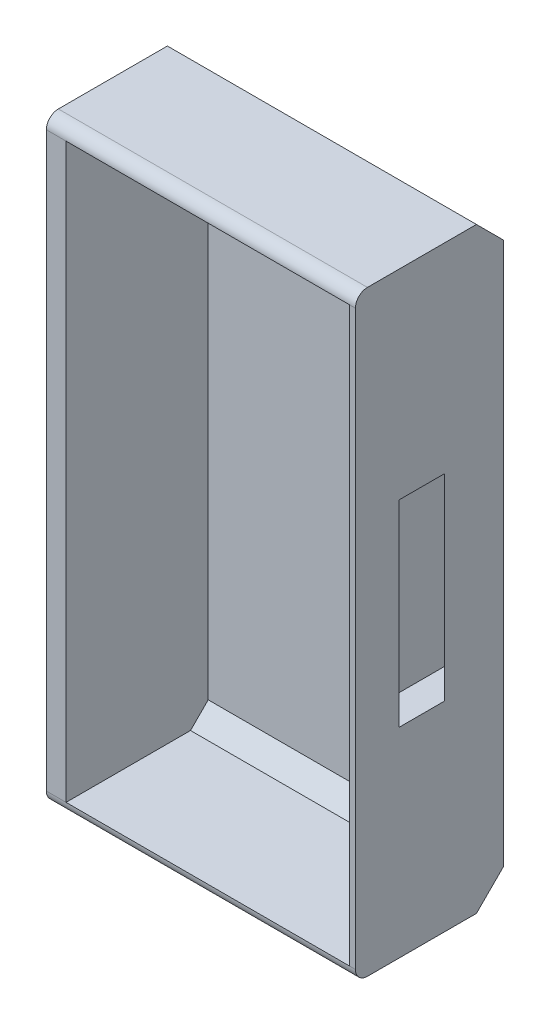
SolidWorks part; units mm, degrees
ref_plane "Front Plane" through (0, 0, 0) normal (1, 0, 0) x (0, 1, 0)
ref_plane "Top Plane" through (0, 0, 0) normal (0, 0, 1) x (0, 1, 0)
ref_plane "Right Plane" through (0, 0, 0) normal (0, 1, 0) x (-1, 0, 0)
sketch "Sketch1" plane through (0, 0, 0) normal (1, 0, 0) x (0, 1, 0)
  line L12 (-98.46, -42.4834) -> (-89.4834, -51.46)
  line L13 (-89.4834, -51.46) -> (89.4834, -51.46)
  line L14 (89.4834, -51.46) -> (98.46, -42.4834)
  line L15 (98.46, -42.4834) -> (98.46, -6.5)
  line L16 (94.5, -2.54) -> (-94.5, -2.54)
  line L17 (-98.46, -6.5) -> (-98.46, -42.4834)
  line L18 (-98.46, -42.4834) -> (-89.4834, -51.46)
  line L19 (-89.4834, -51.46) -> (89.4834, -51.46)
  line L20 (89.4834, -51.46) -> (98.46, -42.4834)
  line L21 (98.46, -42.4834) -> (98.46, -6.5)
  line L22 (94.5, -2.54) -> (-94.5, -2.54)
  line L23 (-98.46, -6.5) -> (-98.46, -42.4834)
  arc A4 (98.46, -6.5) -> (94.5, -2.54) centre (94.5, -6.5) ccw
  arc A5 (-94.5, -2.54) -> (-98.46, -6.5) centre (-94.5, -6.5) ccw
  arc A6 (98.46, -6.5) -> (94.5, -2.54) centre (94.5, -6.5) ccw
  arc A7 (-94.5, -2.54) -> (-98.46, -6.5) centre (-94.5, -6.5) ccw
  dimension "D1" = 0.04
extrude "Boss-Extrude1" add sketch "Sketch1" along normal up to surface (102 mm away) contours L18 L19 L20 L21 A6 L22 A7 L23
ref_plane "Plane3" through (0, 0, 0) normal (0, 1, 0) x (1, 0, 0)
sketch "Sketch11" plane through (0, 0, 0) normal (0, 1, 0) x (1, 0, 0)
  line L0 (102, 24.4917) -> (104.8284, 21.6633)
  line L1 (102, 6.5) -> (102, 42.4834) construction
  line L2 (102, 24.4917) -> (92.1005, 34.3912)
  dimension "D1" = 14
  dimension "D2" = 4
  dimension "D3" = 45
sketch "Sketch12" plane through (102, 0, 0) normal (1, 0, 0) x (0, 1, 0)
  line L0 (0, -24.4917) -> (0, -21.6633) construction
  line L1 (-32.5, -31.9917) -> (32.5, -31.9917)
  line L2 (-32.5, -31.9917) -> (-32.5, -16.9917)
  line L3 (-32.5, -16.9917) -> (32.5, -16.9917)
  line L4 (32.5, -31.9917) -> (32.5, -16.9917)
  line L5 (-32.5, -31.9917) -> (32.5, -16.9917) construction
  line L6 (-32.5, -16.9917) -> (32.5, -31.9917) construction
  line L7 (0, -24.4917) -> (0, -34.3912) construction
  line L10 (89.4834, -51.46) -> (-89.4834, -51.46) construction
  point P0 (0, -24.4917)
  dimension "D1" = 65
  dimension "D2" = 15
  dimension "D3" = 26.9683
sweep "Cut-Sweep1" cut profiles "Sketch12" path "Sketch11"
shell "Shell1" thickness 2 removed face at (51, 0, -2.54)
sketch "Sketch8" plane through (2, 0, 0) normal (1, 0, 0) x (0, 1, 0)
  line L11 (-10, -27) -> (-10, -17)
  line L12 (-10, -17) -> (10, -17)
  line L13 (10, -27) -> (10, -17)
  line L15 (-98.46, -42.4834) -> (-89.4834, -51.46)
  line L16 (-89.4834, -51.46) -> (89.4834, -51.46)
  line L17 (89.4834, -51.46) -> (98.46, -42.4834)
  line L18 (98.46, -42.4834) -> (98.46, -6.5)
  line L19 (94.5, -2.54) -> (-94.5, -2.54)
  line L20 (-98.46, -6.5) -> (-98.46, -42.4834)
  line L21 (-98.46, -42.4834) -> (-89.4834, -51.46)
  line L22 (-89.4834, -51.46) -> (89.4834, -51.46)
  line L23 (89.4834, -51.46) -> (98.46, -42.4834)
  line L24 (98.46, -42.4834) -> (98.46, -6.5)
  line L25 (94.5, -2.54) -> (-94.5, -2.54)
  line L26 (-98.46, -6.5) -> (-98.46, -42.4834)
  arc A0 (-10, -27) -> (10, -27) centre (0, -27) ccw
  arc A5 (98.46, -6.5) -> (94.5, -2.54) centre (94.5, -6.5) ccw
  arc A6 (-94.5, -2.54) -> (-98.46, -6.5) centre (-94.5, -6.5) ccw
  arc A7 (98.46, -6.5) -> (94.5, -2.54) centre (94.5, -6.5) ccw
  arc A8 (-94.5, -2.54) -> (-98.46, -6.5) centre (-94.5, -6.5) ccw
  point P4 (0, -51.46)
  dimension "D2" = 20
  dimension "D3" = 24.46
  dimension "D4" = 10
  dimension "D5" = 20
  dimension "D1" = 0
extrude "Boss-Extrude2" add sketch "Sketch8" along normal blind 2.5
sketch "Sketch10" plane through (4.5, 0, 0) normal (1, 0, 0) x (0, 1, 0)
  line L8 (94.5, -4.54) -> (94.5, -2.54)
  line L9 (94.5, -2.54) -> (-94.5, -2.54)
  line L10 (-94.5, -2.54) -> (-94.5, -4.54)
  line L11 (-96.46, -6.5) -> (-96.46, -41.655)
  line L12 (-96.46, -41.655) -> (-88.655, -49.46)
  line L13 (-88.655, -49.46) -> (88.655, -49.46)
  line L14 (88.655, -49.46) -> (96.46, -41.655)
  line L15 (96.46, -41.655) -> (96.46, -6.5)
  line L16 (94.5, -4.54) -> (94.5, -2.54)
  line L17 (94.5, -2.54) -> (-94.5, -2.54)
  line L18 (-94.5, -2.54) -> (-94.5, -4.54)
  line L19 (-96.46, -6.5) -> (-96.46, -41.655)
  line L20 (-96.46, -41.655) -> (-88.655, -49.46)
  line L21 (-88.655, -49.46) -> (88.655, -49.46)
  line L22 (88.655, -49.46) -> (96.46, -41.655)
  line L23 (96.46, -41.655) -> (96.46, -6.5)
  arc A2 (-94.5, -4.54) -> (-96.46, -6.5) centre (-94.5, -6.5) ccw
  arc A3 (96.46, -6.5) -> (94.5, -4.54) centre (94.5, -6.5) ccw
  arc A4 (-94.5, -4.54) -> (-96.46, -6.5) centre (-94.5, -6.5) ccw
  arc A5 (96.46, -6.5) -> (94.5, -4.54) centre (94.5, -6.5) ccw
  dimension "D1" = 0
extrude "Boss-Extrude3" add sketch "Sketch10" along normal blind 2
chamfer "Chamfer1" distance 20 angle 45 1 edges at (100, 0, -36.8201) first distance on face at (100, 0, -20.8578)
sketch "Sketch13" plane through (6.5, 0, 0) normal (1, 0, 0) x (0, 1, 0)
  line L0 (-94.5, -4.54) -> (-94.5, -43.615)
  line L1 (94.5, -4.54) -> (94.5, -40.0826)
  line L2 (94.5, -40.0826) -> (94.5, -43.615)
  line L8 (94.5, -4.54) -> (94.5, -2.54)
  line L9 (94.5, -2.54) -> (-94.5, -2.54)
  line L10 (-94.5, -2.54) -> (-94.5, -4.54)
  line L11 (-96.46, -6.5) -> (-96.46, -41.655)
  line L12 (-96.46, -41.655) -> (-88.655, -49.46)
  line L13 (-88.655, -49.46) -> (88.655, -49.46)
  line L14 (88.655, -49.46) -> (96.46, -41.655)
  line L15 (96.46, -41.655) -> (96.46, -6.5)
  line L19 (-96.46, -6.5) -> (-96.46, -41.655)
  line L20 (-96.46, -41.655) -> (-94.5, -43.615)
  line L22 (94.5, -43.615) -> (96.46, -41.655)
  line L23 (96.46, -41.655) -> (96.46, -6.5)
  arc A2 (96.46, -6.5) -> (94.5, -4.54) centre (94.5, -6.5) ccw
  arc A3 (-94.5, -4.54) -> (-96.46, -6.5) centre (-94.5, -6.5) ccw
  arc A4 (96.46, -6.5) -> (94.5, -4.54) centre (94.5, -6.5) ccw
  arc A5 (-94.5, -4.54) -> (-96.46, -6.5) centre (-94.5, -6.5) ccw
  dimension "D1" = 0
extrude "Boss-Extrude4" add sketch "Sketch13" along normal up to surface (93.5 mm away) up to face at (100, 0, -24.2732)
